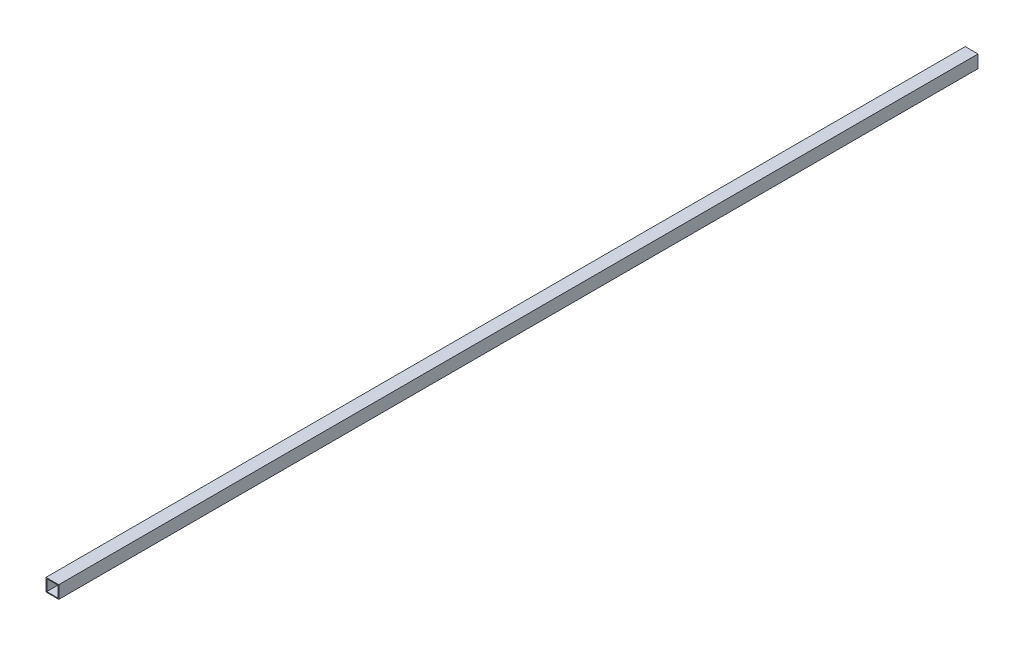
SolidWorks part; units mm, degrees
material "6063-O"
ref_plane "Front Plane" through (0, 0, 0) normal (0, 0, 1) x (1, 0, 0)
ref_plane "Top Plane" through (0, 0, 0) normal (0, 1, 0) x (1, 0, 0)
ref_plane "Right Plane" through (0, 0, 0) normal (1, 0, 0) x (0, 0, -1)
sketch "Sketch1" plane through (0, 0, 0) normal (0, 0, 1) x (1, 0, 0)
  line L1 (-12.7, 12.7) -> (12.7, 12.7)
  line L2 (-12.7, 12.7) -> (-12.7, -12.7)
  line L3 (-12.7, -12.7) -> (12.7, -12.7)
  line L4 (12.7, 12.7) -> (12.7, -12.7)
  line L5 (-12.7, 12.7) -> (12.7, -12.7) construction
  line L6 (-12.7, -12.7) -> (12.7, 12.7) construction
  line L7 (-11.1125, 11.1125) -> (11.1125, 11.1125)
  line L8 (-11.1125, 11.1125) -> (-11.1125, -11.1125)
  line L9 (-11.1125, -11.1125) -> (11.1125, -11.1125)
  line L10 (11.1125, 11.1125) -> (11.1125, -11.1125)
  line L11 (-11.1125, 11.1125) -> (11.1125, -11.1125) construction
  line L12 (-11.1125, -11.1125) -> (11.1125, 11.1125) construction
  point P0 (0, 0)
  point P6 (0, 0)
  dimension "D1" = 25.4
  dimension "D2" = 25.4
  dimension "D3" = 1.5875
extrude "Boss-Extrude1" add sketch "Sketch1" along normal blind 1828.8
